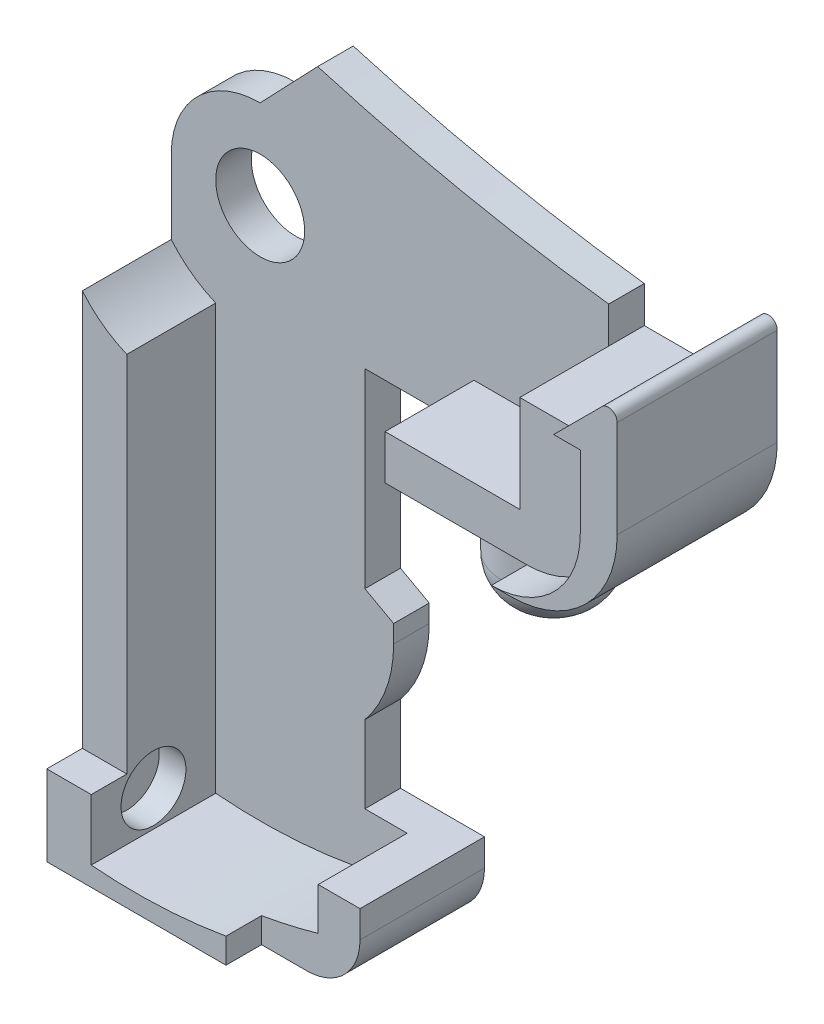
SolidWorks part; units mm, degrees
ref_plane "정면" through (0, 0, 0) normal (0, 0, 1) x (1, 0, 0)
ref_plane "윗면" through (0, 0, 0) normal (0, 1, 0) x (1, 0, 0)
ref_plane "우측면" through (0, 0, 0) normal (1, 0, 0) x (0, 0, -1)
sketch "스케치1" plane through (0, 0, 0) normal (0, 0, 1) x (1, 0, 0)
  line L0 (0, 5) -> (3.2319, 8.3833)
  line L1 (0, 5) -> (19.6, 5)
  line L2 (19.6, 5) -> (19.6, 2.9507)
  line L3 (19.6, 2.9507) -> (23.5, 2.9507)
  line L4 (23.5, 2.9507) -> (23.5, 4.0959)
  line L5 (23.5, 4.0959) -> (25, 4.0959)
  line L6 (25, 4.0959) -> (25, 0)
  line L7 (20, -5) -> (5.8894, -5)
  line L8 (5.8894, -5) -> (5.8894, -26.4376)
  line L9 (-5, -30.9618) -> (7.6137, -30.9618)
  line L10 (-5, -30.9618) -> (-5, 0)
  line L11 (10.6137, -27.9618) -> (10.6137, -26.4376)
  line L12 (10.6137, -26.4376) -> (5.8894, -26.4376)
  line L13 (5.8894, -26.4376) -> (8.2516, -26.4376)
  line L14 (19.6, 2.9507) -> (19.6, -2.5)
  line L15 (19.6, -2.5) -> (12.0232, -2.5)
  line L16 (-2.5, -4.3301) -> (-2.5, -26.4377)
  line L17 (-2.5, -29.8745) -> (-2.5, -26.4377)
  line L18 (-2.5, -26.4377) -> (-5, -26.4377)
  line L19 (5.0761, -29.546) -> (5.0761, -30.9618)
  line L20 (5.8894, -15.7188) -> (5.8894, -26.4376)
  line L21 (8.2649, -26.4376) -> (8.2649, -28.8171)
  line L22 (12.0232, -2.5) -> (12.0232, -5)
  line L23 (5.8894, -15.7188) -> (5.8894, -26.4376)
  line L24 (7.5062, -17.6039) -> (7.5062, -16.6061)
  line L25 (7.5062, -16.6061) -> (5.8894, -15.7188)
  line L26 (23.5, 4.0959) -> (26.2222, 6.8181)
  line L27 (27.0757, 6.4645) -> (27.0757, 1)
  line L28 (21.0757, -5) -> (20, -5)
  circle A0 centre (0, 0) radius 2.5
  circle A1 centre (0, 0) radius 5
  arc A2 (-2.5, -29.8745) -> (8.2649, -28.8171) centre (0, 0) ccw
  arc A3 (-5, -4.1533) -> (-2.5, -6) centre (0, 0) ccw
  arc A4 (19.6, 5) -> (3.2319, 8.3833) centre (32.2465, 107.4683) cw
  arc A5 (25, 0) -> (20, -5) centre (20, 0) cw
  arc A6 (7.5062, -17.6039) -> (5.8894, -22.0908) centre (0.4717, -17.6039) cw
  arc A7 (7.6137, -30.9618) -> (10.6137, -27.9618) centre (7.6137, -27.9618) ccw
  arc A8 (27.0757, 1) -> (21.0757, -5) centre (21.0757, 1) cw
  arc A9 (26.2222, 6.8181) -> (27.0757, 6.4645) centre (26.5757, 6.4645) cw
  point P48 (27.0757, 7.6716)
  dimension "D1" = 5
  dimension "D2" = 19.6
  dimension "D3" = 5
  dimension "D6" = 3
  dimension "D9" = 6
  dimension "D10" = 0.5
  dimension "D4" = 30
  dimension "D5" = 1.5
  dimension "D7" = 5.0568
  dimension "D8" = 45
extrude "보스-돌출3" add sketch "스케치1" along normal blind 9 contours A2 L17 L18 L10 L9 L19 | A9 L26 L5 L6 A5 L28 A8 L27 region at (-3.75, -26.5481, 0) region at (25.5751, 1.3496, 0)
extrude "보스-돌출4" add sketch "스케치1<7>" along normal blind 7 contours A2 L19 L9 L11 | L15 L7 L6 L5 L4 L3 L14 | A1 L10 L18 L16 region at (20.1009, -1.5137, 0) region at (-3.7678, -15.8289, 0) region at (8.3321, -29.0215, 0)
sketch "스케치1<7>" plane through (0, 0, 0) normal (0, 0, 1) x (1, 0, 0) same geometry as "스케치1"
extrude "보스-돌출5" add sketch "스케치1<8>" along normal blind 2 contours L17 A2 L11 L12 L8 L15 L14 L2 L1 A1 L10 L18 | A1 A0 | L10 A3 L16 A1 | L1 A4 L0 | A6 L23 region at (7.1251, 6.0723, 0) region at (5.4727, -10.5859, 0) region at (3.4355, 3.4355, 0) region at (-3.8947, -3.9886, 0) region at (6.5659, -18.5308, 0)
sketch "스케치1<8>" plane through (0, 0, 0) normal (0, 0, 1) x (1, 0, 0) same geometry as "스케치1"
sketch "스케치2" plane through (0, -5, 0) normal (0, -1, 0) x (1, 0, 0)
  circle A0 centre (18, 3.5) radius 2.9
  dimension "D1" = 5.8
extrude "보스-돌출6" add sketch "스케치2" along normal mid plane 4.9
sketch "스케치4" plane through (0, -7.45, 0) normal (0, -1, 0) x (1, 0, 0)
  circle A0 centre (18, 3.5) radius 2.9 construction
  circle A1 centre (18, 3.5) radius 2.9
extrude "보스-돌출7" add sketch "스케치4" along normal blind 2
fillet "필렛2" radius 2.4 1 edges at (18, -9.45, 0.6)
sketch "스케치5" plane through (-2.5, 0, 0) normal (1, 0, 0) x (0, 0, -1)
  line L0 (-9, -29.8745) -> (-2, -29.8745) construction
  circle A0 centre (-5.5, -27.8745) radius 1.825
  point P2 (-5.5, -29.8745)
  dimension "D1" = 3.65
  dimension "D2" = 2
extrude "컷-돌출1" cut sketch "스케치5" against normal blind 1.5
